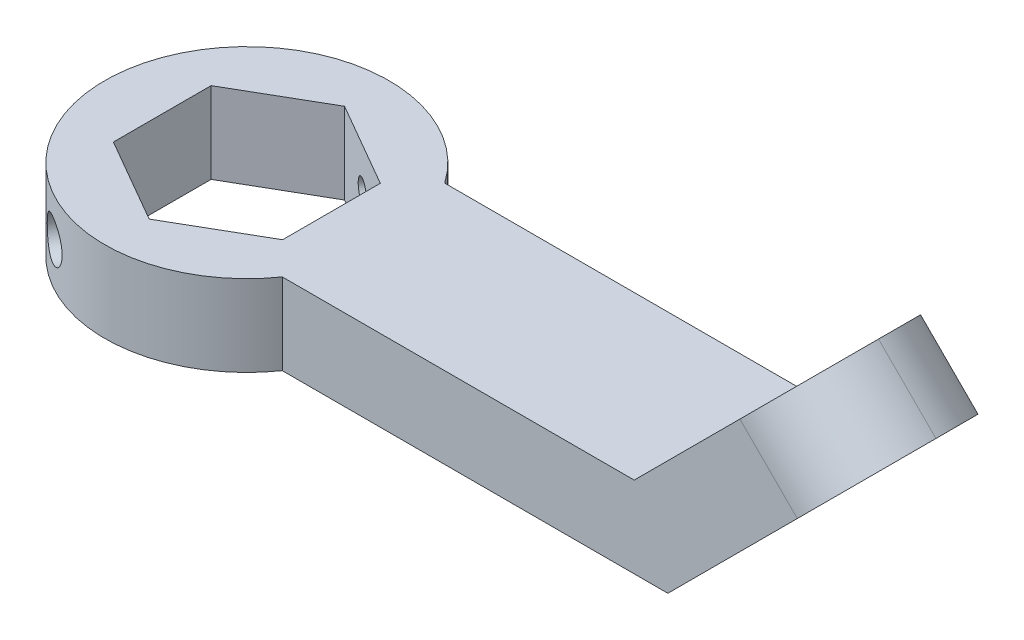
SolidWorks part; units mm, degrees
ref_plane "Front Plane" through (0, 0, 0) normal (0, 0, 1) x (1, 0, 0)
ref_plane "Top Plane" through (0, 0, 0) normal (0, 1, 0) x (1, 0, 0)
ref_plane "Right Plane" through (0, 0, 0) normal (1, 0, 0) x (0, 0, -1)
sketch "Sketch2" plane through (0, 0, 0) normal (0, 0, 1) x (1, 0, 0)
  line L0 (0, 0) -> (74.2, 0) construction
  line L1 (74.2, 0) -> (90.5, 16.3) construction
  dimension "D1" = 16.3
  dimension "D2" = 90.5
  dimension "D3" = 45
sketch "Sketch3" plane through (0, 0, 0) normal (0, 1, 0) x (1, 0, 0)
  line L1 (0, 14.4338) -> (-12.5, 7.2169)
  line L2 (-12.5, 7.2169) -> (-12.5, -7.2169)
  line L3 (-12.5, -7.2169) -> (0, -14.4338)
  line L4 (0, -14.4338) -> (12.5, -7.2169)
  line L5 (12.5, -7.2169) -> (12.5, 7.2169)
  line L6 (12.5, 7.2169) -> (0, 14.4338)
  line L7 (-32.2, -12) -> (74.2, -12)
  line L8 (-32.2, -12) -> (-32.2, 12)
  line L9 (-32.2, 12) -> (74.2, 12)
  line L10 (74.2, -12) -> (74.2, 12)
  line L11 (-32.2, -12) -> (74.2, 12) construction
  line L12 (-32.2, 12) -> (74.2, -12) construction
  circle A0 centre (0, 0) radius 12.5 construction
  circle A1 centre (0, 0) radius 21
  point P10 (21, 0)
  point P18 (74.2, 0)
  dimension "D1" = 25
  dimension "D2" = 42
  dimension "D3" = 24
extrude "Boss-Extrude1" add sketch "Sketch3" along normal blind 12 contours L7 A1 L4 L3 | L7 A1 L9 L6 L5 L4 | L9 A1 L7 L3 L2 L1 | L9 A1 L1 L6 | A1 L7 L10 L9 region at (0, 0, -15.8173) region at (-15.0321, 0, 0) region at (15.0321, 0, 0) region at (46.9854, 0, 0) region at (0, 0, 15.8173)
ref_plane "Plane1" through (37.1, -37.1, 0) normal (0.7071, -0.7071, 0) x (0.7071, 0.7071, 0)
sketch "Sketch4" plane through (37.1, -37.1, 0) normal (0.7071, -0.7071, 0) x (0.7071, 0.7071, 0)
  line L0 (52.4673, 0) -> (75.519, 0) construction
  line L2 (52.4673, 12) -> (91.519, 12)
  line L3 (52.4673, 12) -> (52.4673, -12)
  line L4 (52.4673, -12) -> (91.519, -12)
  line L5 (91.519, 12) -> (91.519, -12)
  circle A0 centre (75.519, 0) radius 8
  circle A1 centre (75.519, 0) radius 4
  dimension "D1" = 16
  dimension "D2" = 8
  dimension "D3" = 24
  dimension "D4" = 16
extrude "Boss-Extrude2" add sketch "Sketch4" against normal blind 12 contours A1 | L2 L5 L4 L3 region at (90.5, 16.3, 0)
extrude "Cut-Extrude1" cut sketch "Sketch4<3>" against normal blind 5.15 contours A0 | A1
sketch "Sketch4<3>" plane through (37.1, -37.1, 0) normal (0.7071, -0.7071, 0) x (0.7071, 0.7071, 0) same geometry as "Sketch4"
fillet "Fillet1" radius 12 2 edges at (97.5711, 31.8563, -12) (97.5711, 31.8563, 12)
sketch "Sketch5" plane through (6.25, 0, -10.8253) normal (-0.5, 0, 0.866) x (0.866, 0, 0.5)
  line L0 (7.2169, 12) -> (-7.2169, 12) construction
  line L1 (7.2169, 12) -> (7.2169, 0) construction
  circle A0 centre (0, 6) radius 3
  circle A1 centre (0, 6) radius 1.7
  point P3 (0, 0)
  point P6 (0, 12)
  point P9 (7.2169, 6)
  dimension "D1" = 3.4
  dimension "D2" = 6
extrude "Cut-Extrude2" cut sketch "Sketch5" against normal through all contours A1
extrude "Cut-Extrude3" cut sketch "Sketch5<3>" against normal through all from offset 5 contours A0 offset against normal yes
sketch "Sketch5<3>" plane through (6.25, 0, -10.8253) normal (-0.5, 0, 0.866) x (0.866, 0, 0.5) same geometry as "Sketch5"
ref_plane "Plane2" through (0, 0, 0) normal (-0.5, 0, 0.866) x (0.866, 0, 0.5)
mirror "Mirror1" about plane through (0, 0, 0) normal (-0.5, 0, 0.866) of "Cut-Extrude2", "Cut-Extrude3"
equation "\"hexD\"=25"
equation "\"D1@Sketch3\"=\"hexD\""
equation "\"D\"=42"
equation "\"D2@Sketch3\"=\"D\""
